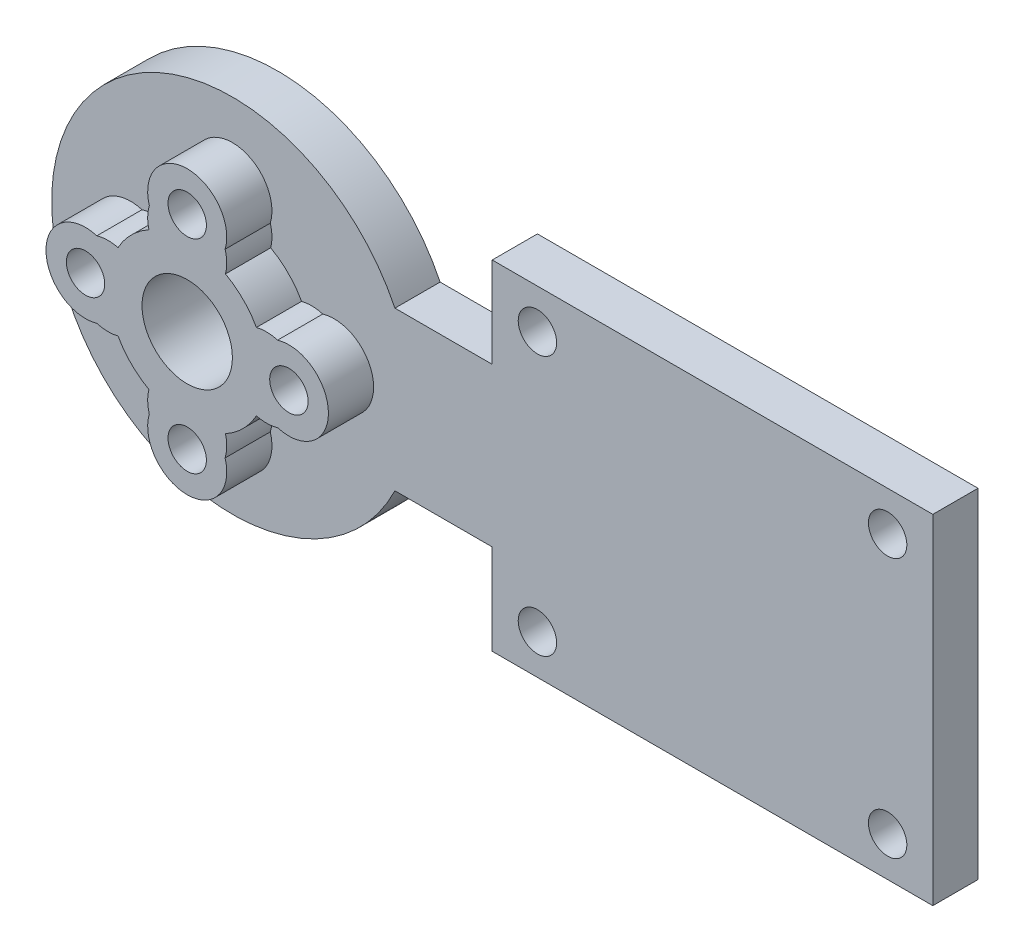
SolidWorks part; units mm, degrees
ref_plane "Front Plane" through (0, 0, 0) normal (0, 0, 1) x (1, 0, 0)
ref_plane "Top Plane" through (0, 0, 0) normal (0, 1, 0) x (1, 0, 0)
ref_plane "Right Plane" through (0, 0, 0) normal (1, 0, 0) x (0, 0, -1)
sketch "Metal_horn_flange_profile" plane through (0, 0, 0) normal (0, 0, 1) x (1, 0, 0)
  circle A0 centre (0, 0) radius 16
  dimension "D1" = 32
extrude "Metal_horn_flange" add sketch "Metal_horn_flange_profile" along normal blind 4
sketch "Straight_forearm_web_profile" plane through (0, 0, 0) normal (0, 0, 1) x (1, 0, 0)
  line L1 (0, -7) -> (28, -7)
  line L2 (0, -7) -> (0, 7)
  line L3 (0, 7) -> (28, 7)
  line L4 (28, -7) -> (28, 7)
  dimension "D1" = 28
  dimension "D2" = 14
  dimension "D3" = 7
extrude "Straight_forearm_web" add sketch "Straight_forearm_web_profile" along normal blind 4
sketch "Replaceable_tool_mounting_deck_profile" plane through (0, 0, 0) normal (0, 0, 1) x (1, 0, 0)
  line L1 (23, -15) -> (62, -15)
  line L2 (23, -15) -> (23, 15)
  line L3 (23, 15) -> (62, 15)
  line L4 (62, -15) -> (62, 15)
  dimension "D1" = 39
  dimension "D2" = 30
  dimension "D3" = 23
  dimension "D4" = 15
extrude "Replaceable_tool_mounting_deck" add sketch "Replaceable_tool_mounting_deck_profile" along normal blind 4
sketch "Dowel_support_hub_profile" plane through (0, 0, 0) normal (0, 0, 1) x (1, 0, 0)
  circle A0 centre (0, 0) radius 7
  circle A1 centre (0, 0) radius 4
  dimension "D1" = 14
  dimension "D2" = 8
extrude "Dowel_support_hub" add sketch "Dowel_support_hub_profile" along normal blind 4 from offset 4
sketch "Raised_washer_seats_PCD14" plane through (0, 0, 0) normal (0, 0, 1) x (1, 0, 0)
  circle A0 centre (7, 0) radius 3.5
  circle A1 centre (-7, 0) radius 3.5
  circle A2 centre (0, 7) radius 3.5
  circle A3 centre (0, -7) radius 3.5
  dimension "D1" = 7
  dimension "D2" = 7
  dimension "D3" = 7
  dimension "D4" = 7
  dimension "D5" = 7
  dimension "D6" = 7
  dimension "D7" = 7
  dimension "D8" = 7
extrude "Washer_seats_clear_dowel_sleeve" add sketch "Raised_washer_seats_PCD14" along normal blind 4 from offset 4
sketch "Metal_horn_M3_pattern_profile" plane through (0, 0, 0) normal (0, 0, 1) x (1, 0, 0)
  circle A0 centre (7, 0) radius 1.6
  circle A1 centre (-7, 0) radius 1.6
  circle A2 centre (0, 7) radius 1.6
  circle A3 centre (0, -7) radius 1.6
  dimension "D1" = 3.2
  dimension "D2" = 3.2
  dimension "D3" = 3.2
  dimension "D4" = 3.2
  dimension "D5" = 7
  dimension "D6" = 7
  dimension "D7" = 7
  dimension "D8" = 7
extrude "Metal_horn_M3_pattern_SUPERSEDED_owned_servo" [suppressed] cut sketch "Metal_horn_M3_pattern_profile" along normal through all from offset 50 offset against normal yes
sketch "Elbow_sleeve_bore_profile" plane through (0, 0, 0) normal (0, 0, 1) x (1, 0, 0)
  circle A0 centre (0, 0) radius 4
  dimension "D1" = 8
extrude "Elbow_sleeve_bore" cut sketch "Elbow_sleeve_bore_profile" along normal through all from offset 50 offset against normal yes
sketch "Modular_tool_four_M3_pattern_profile" plane through (0, 0, 0) normal (0, 0, 1) x (1, 0, 0)
  circle A0 centre (27, -11.5) radius 1.7
  circle A1 centre (27, 11.5) radius 1.7
  circle A2 centre (58, -11.5) radius 1.7
  circle A3 centre (58, 11.5) radius 1.7
  dimension "D1" = 3.4
  dimension "D2" = 3.4
  dimension "D3" = 3.4
  dimension "D4" = 3.4
  dimension "D5" = 27
  dimension "D6" = 58
  dimension "D7" = 11.5
  dimension "D8" = 11.5
extrude "Modular_tool_four_M3_pattern" cut sketch "Modular_tool_four_M3_pattern_profile" along normal through all from offset 50 offset against normal yes
sketch "Printed_hub_washer_seats_PCD18_profile" plane through (0, 0, 0) normal (0, 0, 1) x (1, 0, 0)
  circle A0 centre (9, 0) radius 3.5
  circle A1 centre (0, 9) radius 3.5
  circle A2 centre (-9, 0) radius 3.5
  circle A3 centre (0, -9) radius 3.5
  dimension "D1" = 7
  dimension "D2" = 7
  dimension "D3" = 7
  dimension "D4" = 7
  dimension "D5" = 9
  dimension "D6" = 9
  dimension "D7" = 9
  dimension "D8" = 9
extrude "Printed_hub_M3_washer_seats_PCD18" add sketch "Printed_hub_washer_seats_PCD18_profile" along normal blind 4 from offset 4
sketch "Printed_hub_M3_clearance_PCD18_profile" plane through (0, 0, 0) normal (0, 0, 1) x (1, 0, 0)
  circle A0 centre (9, 0) radius 1.7
  circle A1 centre (0, 9) radius 1.7
  circle A2 centre (-9, 0) radius 1.7
  circle A3 centre (0, -9) radius 1.7
  dimension "D1" = 3.4
  dimension "D2" = 3.4
  dimension "D3" = 3.4
  dimension "D4" = 3.4
  dimension "D5" = 9
  dimension "D6" = 9
  dimension "D7" = 9
  dimension "D8" = 9
extrude "Printed_hub_M3_clearance_PCD18" cut sketch "Printed_hub_M3_clearance_PCD18_profile" along normal through all from offset 50 offset against normal yes
